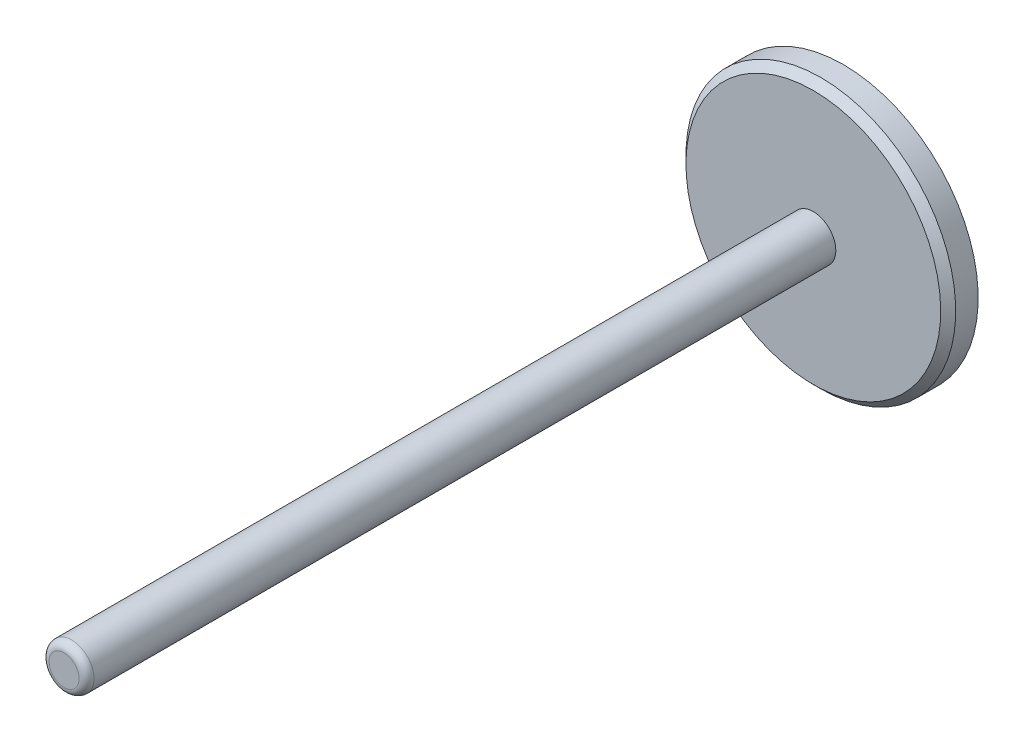
SolidWorks part; units mm, degrees
material "Chrome Stainless Steel"
ref_plane "Front Plane" through (0, 0, 0) normal (1, 0, 0) x (0, 1, 0)
ref_plane "Top Plane" through (0, 0, 0) normal (0, 0, 1) x (0, 1, 0)
ref_plane "Right Plane" through (0, 0, 0) normal (0, 1, 0) x (-1, 0, 0)
sketch "Sketch1" plane through (0, 0, 0) normal (1, 0, 0) x (0, 1, 0)
  line L0 (0, -11.3701) -> (0, -6.7928) construction
  line L1 (-6.1169, 0) -> (6.3124, 0) construction
  line L2 (0, 0) -> (0, 50)
  line L3 (0, 50) -> (1.5, 50)
  line L4 (1.5, 50) -> (1.5, 0)
  line L5 (1.5, 0) -> (0, 0)
  line L6 (0, 0) -> (9, 0)
  line L7 (9, 0) -> (9, -2)
  line L8 (9, -2) -> (0, -2)
  line L9 (0, -2) -> (0, 0)
  line L10 (1.5, 0) -> (9, 0)
  dimension "D1" = 18
  dimension "D2" = 50
  dimension "D3" = 3
  dimension "D4" = 2
revolve "Revolve1" add sketch "Sketch1" angle 360 about L0 region at (0, 0.75, 25) region at (0, 4.5, -1)
fillet "Fillet1" radius 0.5 1 edges at (0, 1.5, 50)
chamfer "Chamfer1" distance 0.5 angle 45 1 edges at (0, 9, 0)
ref_axis "Axis1" through (0, 0, 49.5) along (0, 0, -1)
